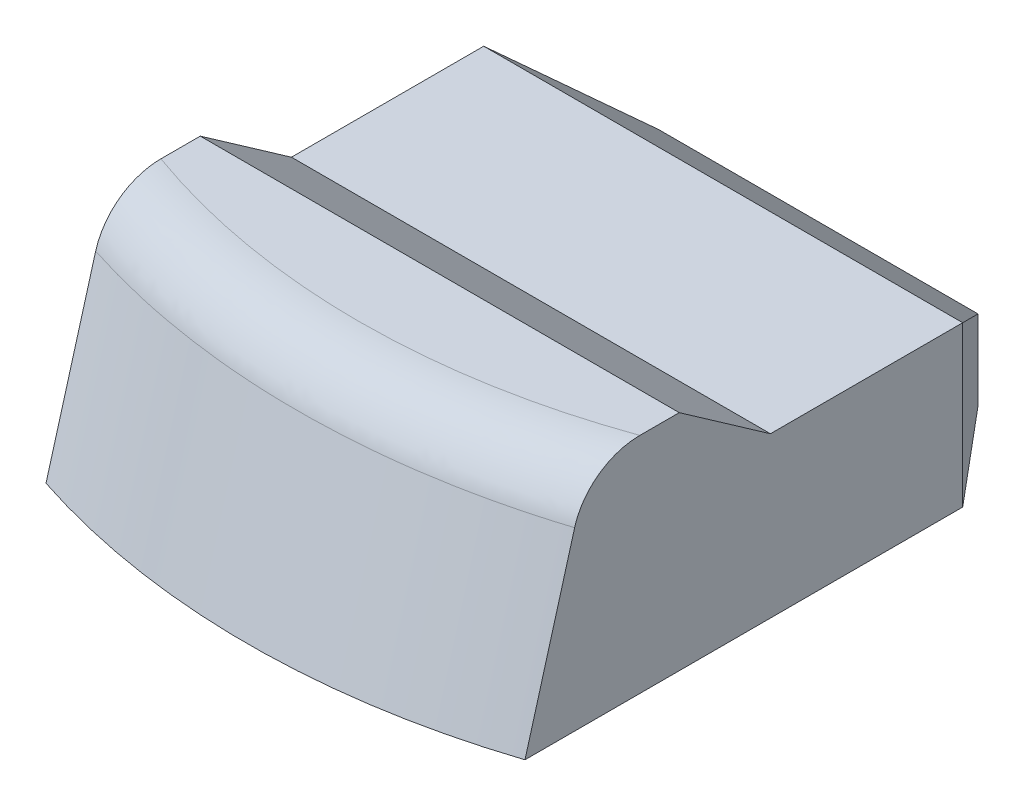
SolidWorks part; units mm, degrees
ref_plane "前视基准面" through (0, 0, 0) normal (0, 0, 1) x (1, 0, 0)
ref_plane "上视基准面" through (0, 0, 0) normal (0, 1, 0) x (1, 0, 0)
ref_plane "右视基准面" through (0, 0, 0) normal (1, 0, 0) x (0, 0, -1)
sketch "草图1" plane through (0, 0, 0) normal (0, 1, 0) x (1, 0, 0)
  line L5 (-1.5, 1) -> (1.5, 1)
  line L6 (-1.5, 1) -> (-1.5, -2.8)
  line L7 (-1.5, -2.8) -> (1.5, -2.8)
  line L8 (1.5, 1) -> (1.5, -2.8)
  point P4 (0, 1)
  dimension "D1" = 3
  dimension "D2" = 1
  dimension "D3" = 3.8
extrude "凸台-拉伸1" add sketch "草图1" along normal blind 1
sketch "草图2" plane through (0, 1, 0) normal (0, 1, 0) x (1, 0, 0)
  line L0 (1.5, -2.8) -> (1.5, 1) construction
  line L1 (-1.5, -2.8) -> (1.5, -2.8)
  line L2 (-1.5, -2.8) -> (-1.5, -0.8)
  line L3 (-1.5, -0.8) -> (1.5, -0.8)
  line L4 (1.5, -2.8) -> (1.5, -0.8)
  dimension "D1" = 2
extrude "凸台-拉伸2" add sketch "草图2" along normal blind 1
chamfer "倒角1" distance 0.5 angle 50 3 edges at (1.5, 0.5, -1) (-1.5, 0.5, -1) (0, 1, -1) first distance on face at (0, 0.5, -1)
sketch "草图3" plane through (0, 0, 2.8) normal (0, 0, 1) x (1, 0, 0)
  line L0 (-0.75, 1) -> (0.75, 1) construction
  line L1 (-0.75, 2) -> (0.75, 2)
  line L2 (-0.75, 0) -> (0.75, 0)
  line L3 (-1.5, 2) -> (1.5, 2) construction
  line L4 (-1.5, 0) -> (1.5, 0) construction
  line L5 (0, 1) -> (0, 0) construction
  arc A0 (-0.75, 2) -> (-0.75, 0) centre (-0.75, 1) ccw
  arc A1 (0.75, 0) -> (0.75, 2) centre (0.75, 1) ccw
  point P2 (0, 1)
  dimension "D1" = 1.5
chamfer "倒角3" distance 1 angle 55 1 edges at (0, 2, 0.8) first distance on face at (0, 1.5, 0.8)
sketch "草图4" plane through (0, 0, 0) normal (0, -1, 0) x (1, 0, 0)
  line L0 (1.6, 2.3034) -> (2.0905, 2.7939)
  line L1 (2.0905, 2.7939) -> (1.7359, 4.0872)
  line L2 (1.7359, 4.0872) -> (1.7194, 4.0898)
  line L3 (1.7194, 4.0898) -> (-1.6729, 4.0898)
  line L4 (-1.6729, 4.0898) -> (-1.9105, 3.4862)
  line L5 (-1.9105, 3.4862) -> (-2.191, 2.5703)
  line L6 (-2.191, 2.5703) -> (-1.6, 2.3034)
  arc A0 (1.6, 2.3034) -> (-1.6, 2.3034) centre (0, -2.2336) ccw construction
  arc A1 (1.6, 2.3034) -> (-1.6, 2.3034) centre (0, -2.2336) ccw
  point P7 (-1.9105, 3.4862)
  point P10 (1.7359, 4.0872)
  point P11 (0.184, 4.3312)
  point P12 (0, 0)
  point P13 (-4.3791, 4.4094)
  point P14 (-1.6729, 4.0898)
sketch "草图6" plane through (1.5, 0, 0) normal (1, 0, 0) x (0, 0, -1)
  line L0 (-2.5703, 0) -> (-2.0085, 1.9932) construction
  line L1 (-2.5703, 0) -> (-2.3034, 0) construction
  point P4 (0, 0)
  point P5 (0, 0)
  point P7 (-2.2281, 2)
  point P8 (-1.8888, 1.9403)
  point P9 (-2.0085, 1.9932)
extrude "切除-拉伸1" cut sketch "草图4" along direction (0, 0.9625, -0.2713) on the side against the normal blind 3.4 contours L4 L5 L6 A1 L0 L1 L2 L3
sketch "草图7" plane through (0, 1, 0) normal (0, 1, 0) x (1, 0, 0)
  line L1 (2.7164, -3.5324) -> (-2.6987, -3.5324)
  line L2 (2.7164, -3.5324) -> (2.7164, 0.3027)
  line L3 (2.7164, 0.3027) -> (-2.6987, 0.3027)
  line L4 (-2.6987, -3.5324) -> (-2.6987, 0.3027)
extrude "切除-拉伸2" cut sketch "草图7" along normal blind 3.4 from offset 0.4
fillet "圆角1" radius 0.4 1 edges at (-0.0743, 1.4, 2.1821)
